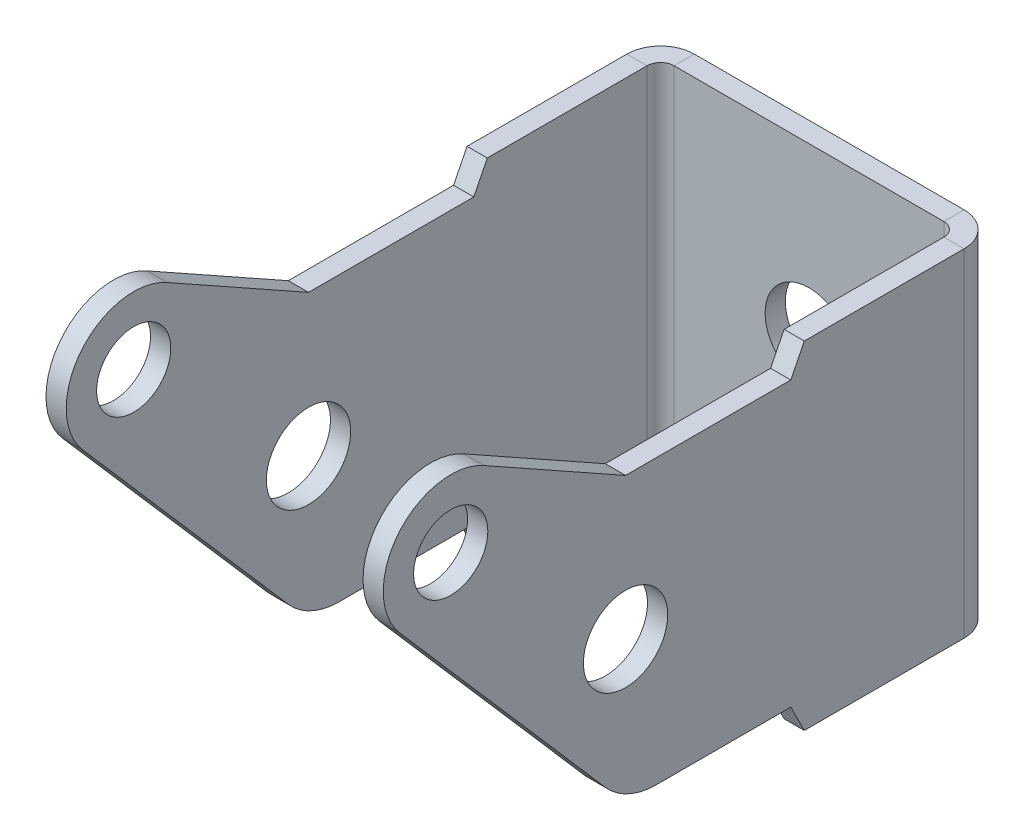
SolidWorks part; units mm, degrees
note: The reader was unsure of these and kept them because the rebuilt part matched: flange length of "Edge-Flange1".
ref_plane "Front Plane" through (0, 0, 0) normal (0, 0, 1) x (1, 0, 0)
ref_plane "Top Plane" through (0, 0, 0) normal (0, 1, 0) x (1, 0, 0)
ref_plane "Right Plane" through (0, 0, 0) normal (1, 0, 0) x (0, 0, -1)
sketch "Sketch1" plane through (0, 0, 0) normal (0, 0, 1) x (1, 0, 0)
  line L1 (-25, 25) -> (25, 25)
  line L2 (-25, 25) -> (-25, -25)
  line L3 (-25, -25) -> (25, -25)
  line L4 (25, 25) -> (25, -25)
  line L5 (-25, 25) -> (25, -25) construction
  line L6 (-25, -25) -> (25, 25) construction
  point P0 (0, 0)
  point P6 (0, 0)
  dimension "D1" = 50
  dimension "D2" = 50
base flange "Base-Flange2" sketch "Sketch1" thickness 3 reverse thickness direction no parameters "D1"=2
edge flange "Edge-Flange1" sketch "Sketch18" flange angle 90 flange length 88.6358 flange position material inside bend radius 2 thickness 3 relief obround parameters "D6"=10
sketch "Sketch18" plane through (25, 0, 0) normal (1, 0, 0) x (0, 1, 0)
  line L0 (-25, 0) -> (25, 0) construction
  line L1 (-25, 0) -> (25, 0)
  line L5 (0, 0) -> (0, 116.9594) construction
  line L6 (25, 0) -> (25, 25.69)
  line L7 (21, 27.69) -> (21, 52.19)
  line L8 (25, -3) -> (-25, -3) construction
  line L9 (25, 25.69) -> (21, 27.69)
  line L10 (-25, 25.69) -> (-25, 0)
  line L11 (-25, 25.69) -> (-21, 27.69)
  line L12 (-21, 27.69) -> (-21, 47.6327)
  line L13 (-80.9249, 52.19) -> (38.9249, 52.19) construction
  line L14 (-17.5606, 55.1798) -> (17.475, 85.6358)
  line L15 (21, 52.19) -> (32.7315, 73.1296)
  line L16 (18.56, 78.11) -> (29.56, 78.11) construction
  line L17 (24.06, 91.0232) -> (24.06, 72.61) construction
  arc A0 (-21, 47.6327) -> (-17.5606, 55.1798) centre (-11, 47.6327) cw
  circle A1 centre (0, 52.19) radius 6.25
  circle A2 centre (24.06, 78.11) radius 5.5
  arc A3 (32.7315, 73.1296) -> (17.475, 85.6358) centre (24.06, 78.11) ccw
  point P17 (-21, 52.19)
  point P20 (-21, 52.19)
  dimension "D6" = 10
  dimension "D7" = 12.5
  dimension "D11" = 11
  dimension "D12" = 20
  dimension "D1" = 25.69
  dimension "D2" = 30.69
  dimension "D3" = 24.5
  dimension "D4" = 21
  dimension "D5" = 229
  dimension "D8" = 150.74
  dimension "D9" = 25.92
  dimension "D10" = 24.06
bend "EdgeBend1" bend radius 2 bend angle 90 parameters "D5"=1
mirror "Mirror1" about plane through (0, 0, 0) normal (1, 0, 0) of "Edge-Flange1"
bend "MirrorBend1" bend radius 2 bend angle 90 parameters "D5"=2
sketch "Sketch22" plane through (0, 0, -3) normal (0, 0, -1) x (-1, 0, 0)
  circle A0 centre (0, 0) radius 6.5
  dimension "D1" = 13
extrude "Cut-Extrude1" cut sketch "Sketch22" against normal blind 10 normal cut yes
sketch "Bend-Lines3" [suppressed] plane through (0, 0, 0) normal (0, 1, 0) x (1, 0, 0)
sketch "Bounding-Box3" [suppressed] plane through (0, 0, 0) normal (0, 1, 0) x (1, 0, 0)
sheet metal parameters "Sheet-Metal2" thickness 3 parameters "D1"=2
flat pattern "Flat-Pattern2" [suppressed]
sketch "Bend-Lines4" plane through (0, 0, 0) normal (0, 1, 0) x (1, 0, 0)
sketch3d "Bounding-Box4" [suppressed]
  line L0 (25, -25, 0) -> (-25, -25, 0) construction
  line L1 (25, 25, 0) -> (-25, 25, 0) construction
  line L2 (25, -25, 0) -> (25, 25, 0) construction
  line L3 (-25, -25, 0) -> (-25, 25, 0) construction
sheet metal parameters "Sheet-Metal3" thickness 3 parameters "D1"=2
flat pattern "Flat-Pattern2"
sketch "Bend-Lines4" plane through (0, 0, 0) normal (0, 0, 1) x (1, 0, 0)
  line L0 (22.7489, -25) -> (22.7489, 25) construction
  line L1 (22.7489, -25) -> (22.7489, 25) construction
sketch3d "Bounding-Box4" [suppressed]
  line L0 (-24.6199, -30.2966, 0) -> (114.8162, -20.2903, 0) construction
  line L1 (-28.5697, 24.7438, 0) -> (110.8663, 34.7501, 0) construction
  line L2 (-24.6199, -30.2966, 0) -> (-28.5697, 24.7438, 0) construction
  line L3 (114.8162, -20.2903, 0) -> (110.8663, 34.7501, 0) construction
bend of the flat pattern "Flatten-<EdgeBend1>1"
sheet metal parameters "Sheet-Metal4" thickness 3 parameters "D1"=2
flat pattern "Flat-Pattern2"
sketch "Bend-Lines4" plane through (0, 0, 0) normal (0, 0, 1) x (1, 0, 0)
  line L0 (22.7489, -25) -> (22.7489, 25) construction
  line L1 (22.7489, -25) -> (22.7489, 25) construction
  line L2 (-22.7489, 25) -> (-22.7489, -25) construction
  line L3 (-22.7489, 25) -> (-22.7489, -25) construction
sketch3d "Bounding-Box4" [suppressed]
  line L0 (-111.6078, -25, 0) -> (111.6078, -25, 0) construction
  line L1 (-111.6078, 34.06, 0) -> (111.6078, 34.06, 0) construction
  line L2 (-111.6078, -25, 0) -> (-111.6078, 34.06, 0) construction
  line L3 (111.6078, -25, 0) -> (111.6078, 34.06, 0) construction
bend of the flat pattern "Flatten-<EdgeBend1>1"
bend of the flat pattern "Flatten-<MirrorBend1>1"
sheet metal parameters "Sheet-Metal5" thickness 3 parameters "D1"=2
flat pattern "Flat-Pattern2"
sketch "Bend-Lines4" plane through (0, 0, 0) normal (0, 0, 1) x (1, 0, 0)
  line L0 (22.7489, -25) -> (22.7489, 25) construction
  line L1 (22.7489, -25) -> (22.7489, 25) construction
  line L2 (-22.7489, 25) -> (-22.7489, -25) construction
  line L3 (-22.7489, 25) -> (-22.7489, -25) construction
sketch3d "Bounding-Box4" [suppressed]
  line L0 (-111.6078, -25, 0) -> (111.6078, -25, 0) construction
  line L1 (-111.6078, 34.06, 0) -> (111.6078, 34.06, 0) construction
  line L2 (-111.6078, -25, 0) -> (-111.6078, 34.06, 0) construction
  line L3 (111.6078, -25, 0) -> (111.6078, 34.06, 0) construction
bend of the flat pattern "Flatten-<EdgeBend1>1"
bend of the flat pattern "Flatten-<MirrorBend1>1"
